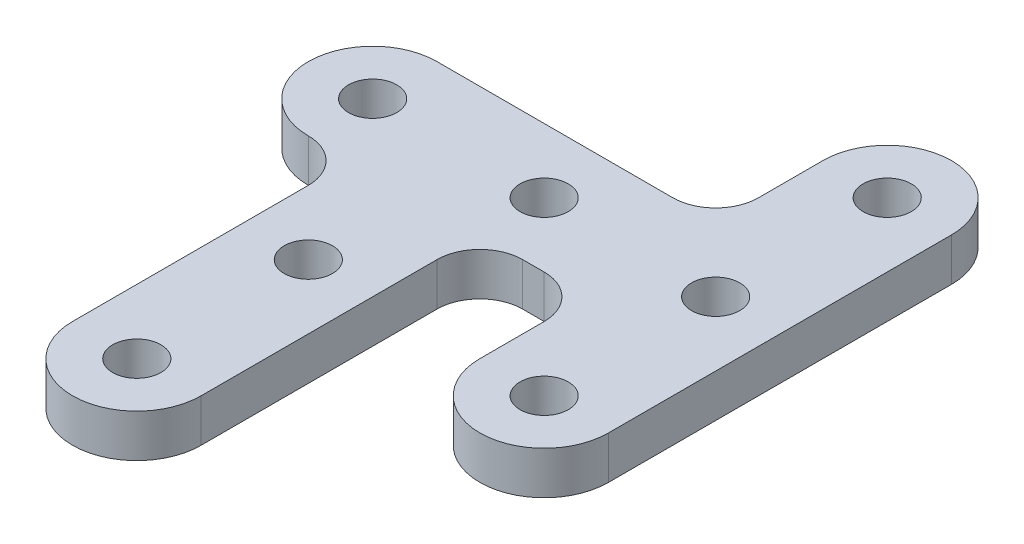
SolidWorks part; units mm, degrees
ref_plane "Front Plane" through (0, 0, 0) normal (0, 0, 1) x (1, 0, 0)
ref_plane "Top Plane" through (0, 0, 0) normal (0, 1, 0) x (1, 0, 0)
ref_plane "Right Plane" through (0, 0, 0) normal (1, 0, 0) x (0, 0, -1)
sketch "Sketch5" plane through (0, 144.9046, 0) normal (0, -1, 0) x (-1, 0, 0)
  line L0 (-124.4918, -1137.9753) -> (-124.4918, -1087.1753) construction
  line L1 (-105.4418, -1103.0503) -> (-105.4418, -1087.1753) construction
  line L2 (-64.1668, -1103.0503) -> (-105.4418, -1103.0503) construction
  line L3 (-70.5168, -1122.1003) -> (-70.5168, -1163.3753) construction
  line L4 (-64.1668, -1122.1003) -> (-70.5168, -1122.1003) construction
  line L5 (-89.5668, -1163.3753) -> (-89.5668, -1122.1003) construction
  line L6 (-89.5668, -1122.1003) -> (-105.4418, -1122.1003) construction
  line L7 (-105.4418, -1122.1003) -> (-105.4418, -1137.9753) construction
  line L8 (-124.4918, -1137.9753) -> (-124.4918, -1087.1753)
  line L9 (-105.4418, -1103.0503) -> (-105.4418, -1087.1753)
  line L10 (-64.1668, -1103.0503) -> (-105.4418, -1103.0503)
  line L11 (-70.5168, -1122.1003) -> (-70.5168, -1163.3753)
  line L12 (-64.1668, -1122.1003) -> (-70.5168, -1122.1003)
  line L13 (-89.5668, -1163.3753) -> (-89.5668, -1122.1003)
  line L14 (-89.5668, -1122.1003) -> (-105.4418, -1122.1003)
  line L15 (-105.4418, -1122.1003) -> (-105.4418, -1137.9753)
  circle A0 centre (-114.9668, -1137.9753) radius 9.525 construction
  circle A1 centre (-114.9668, -1087.1753) radius 9.525 construction
  circle A2 centre (-80.0418, -1163.3753) radius 9.525 construction
  circle A3 centre (-64.1668, -1112.5753) radius 9.525 construction
  arc A4 (-124.4918, -1137.9753) -> (-105.4418, -1137.9753) centre (-114.9668, -1137.9753) ccw
  arc A5 (-105.4418, -1087.1753) -> (-124.4918, -1087.1753) centre (-114.9668, -1087.1753) ccw
  arc A6 (-89.5668, -1163.3753) -> (-70.5168, -1163.3753) centre (-80.0418, -1163.3753) ccw
  arc A7 (-64.1668, -1122.1003) -> (-64.1668, -1103.0503) centre (-64.1668, -1112.5753) ccw
extrude "Boss-Extrude2" add sketch "Sketch5" along normal up to vertex (19.177 mm away) from vertex at 12.827
hole_wizard "1/4 Clearance Hole2" positions "Sketch6" profile "Sketch7" hole size "1/4" standard "ANSI Inch" end condition through all
sketch "Sketch6" plane through (0, 125.7276, 0) normal (0, -1, 0) x (-1, 0, 0)
  point P0 (-114.9668, -1087.1753)
  point P3 (-114.9668, -1137.9753)
  point P6 (-114.9668, -1112.5753)
  point P9 (-89.5668, -1112.5753)
  point P12 (-64.1668, -1112.5753)
  point P15 (-80.0418, -1137.9753)
  point P18 (-80.0418, -1163.3753)
sketch "Sketch7" plane through (114.9668, 125.7276, 1087.1753) normal (1, 0, 0) x (0, 0, -1)
  line L0 (0, 0) -> (0, 6.35)
  line L1 (0, 6.35) -> (3.5712, 6.35)
  line L2 (3.5712, 6.35) -> (3.5712, 0)
  line L5 (3.5712, 0) -> (0, 0)
  line L11 (0, -6.35) -> (0, 107.95) construction
  dimension "Thru Hole Dia." = 7.1425
  dimension "Thru Hole Depth" = 6.35
fillet "Fillet2" radius 6.35 4 edges at (105.4418, 128.9026, 1103.0503) (89.5668, 128.9026, 1122.1003) (105.4418, 128.9026, 1122.1003) (70.5168, 128.9026, 1122.1003)
